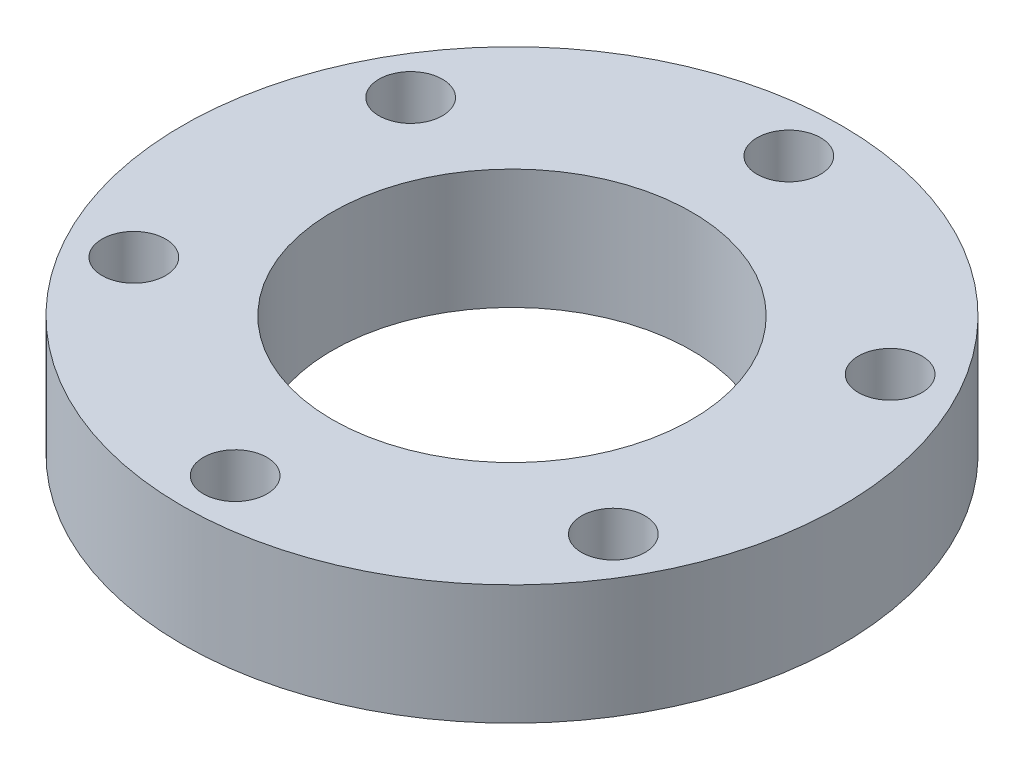
SolidWorks part; units mm, degrees
ref_plane "Front Plane" through (0, 0, 0) normal (0, 0, 1) x (1, 0, 0)
ref_plane "Top Plane" through (0, 0, 0) normal (0, 1, 0) x (1, 0, 0)
ref_plane "Right Plane" through (0, 0, 0) normal (1, 0, 0) x (0, 0, -1)
sketch "Sketch1" plane through (0, 0, 0) normal (0, 1, 0) x (1, 0, 0)
  circle A0 centre (0, 0) radius 34.925
  dimension "D1" = 69.85
extrude "Extrude1" add sketch "Sketch1" along normal blind 12.7
sketch "Sketch2" plane through (0, 0, 0) normal (0, 1, 0) x (1, 0, 0)
  circle A0 centre (0, 0) radius 19.05
  dimension "D1" = 38.1
extrude "Cut-Extrude1" cut sketch "Sketch2" along normal through all
sketch "Sketch3" plane through (0, 0, 0) normal (0, 1, 0) x (1, 0, 0)
  circle A0 centre (0, 29.337) radius 3.3655
  dimension "D1" = 6.731
  dimension "D2" = 29.337
extrude "Cut-Extrude2" cut sketch "Sketch3" along normal through all
ref_axis "Axis1" through (0, 35.8582, 0) along (0, -1, 0)
pattern_circular "CirPattern1" count 6 over 360 about axis through (0, 35.8582, 0) along (0, -1, 0) of "Cut-Extrude2"
sketch "Sketch4" plane through (0, 0, 0) normal (0, 1, 0) x (1, 0, 0)
  line L0 (0, 0) -> (0, 16.8619)
ref_plane "Plane1" through (0, 0, 0) normal (0, -1, 0) x (1, 0, 0)
sketch "Sketch5" plane through (0, 0, 0) normal (0, -1, 0) x (1, 0, 0)
  circle A0 centre (0, 0) radius 4.7625
  dimension "D1" = 9.525
